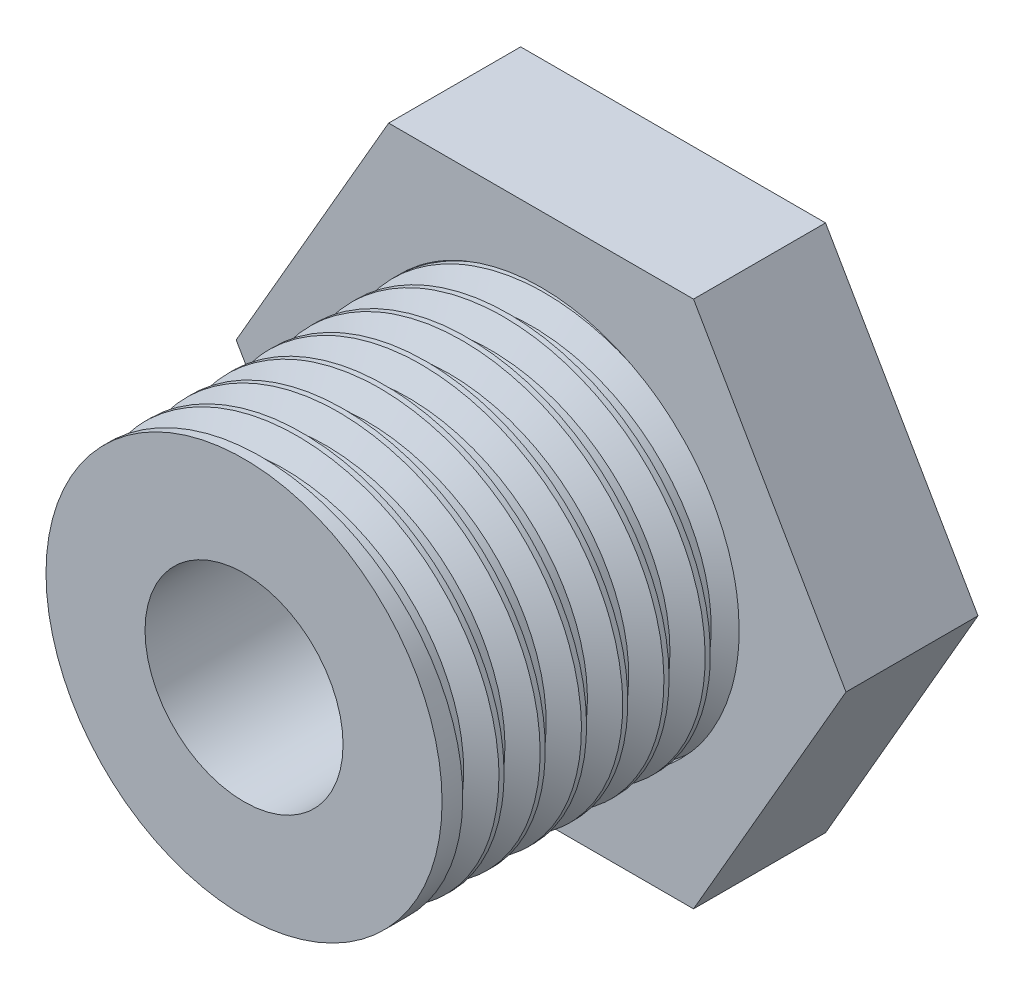
SolidWorks part; units mm, degrees
ref_plane "Front Plane" through (0, 0, 0) normal (0, 0, 1) x (1, 0, 0)
ref_plane "Top Plane" through (0, 0, 0) normal (0, 1, 0) x (1, 0, 0)
ref_plane "Right Plane" through (0, 0, 0) normal (1, 0, 0) x (0, 0, -1)
sketch "Sketch1" plane through (0, 0, 0) normal (0, 0, 1) x (1, 0, 0)
  line L1 (9.2376, 0) -> (4.6188, 8)
  line L2 (4.6188, 8) -> (-4.6188, 8)
  line L3 (-4.6188, 8) -> (-9.2376, 0)
  line L4 (-9.2376, 0) -> (-4.6188, -8)
  line L5 (-4.6188, -8) -> (4.6188, -8)
  line L6 (4.6188, -8) -> (9.2376, 0)
  circle A0 centre (0, 0) radius 8 construction
  dimension "D1" = 16
extrude "Boss-Extrude1" add sketch "Sketch1" along normal blind 4
sketch "Sketch2" plane through (0, 0, 4) normal (0, 0, 1) x (1, 0, 0)
  circle A0 centre (0, 0) radius 6
  dimension "D1" = 12
extrude "Boss-Extrude2" add sketch "Sketch2" along normal blind 9
sketch "Sketch3" plane through (0, 0, 13) normal (0, 0, 1) x (1, 0, 0)
  circle A0 centre (0, 0) radius 3
  dimension "D1" = 6
extrude "Cut-Extrude1" cut sketch "Sketch3" against normal through all
thread "Thread1" pitch 1.25 start angle 0, offset 0, length 9, pitch 1.25, diameter 12
ref_plane "Plane1" through (-6, 0, 13) normal (0, -1, 0) x (-1, 0, 0)
sketch "Thread Profile1" plane through (-6, 0, 13) normal (0, -1, 0) x (-1, 0, 0)
  line L0 (0, 0) -> (0, 1.25) construction
  line L11 (0, 0) -> (0, 1.0937)
  line L12 (0, 1.0937) -> (-0.6766, 0.7031)
  line L13 (-0.6766, 0.7031) -> (-0.6766, 0.3906)
  line L15 (-0.6766, 0.3906) -> (0, 0)
  line L17 (-0.6766, 0.5469) -> (0, 0.5469) construction
  point P2 (0, 0)
  dimension "Pitch" = 1.25
  dimension "Profile_Angle" = 60
  dimension "Profile_Land" = 0.3125
  dimension "Profile_Height" = 0.6766
